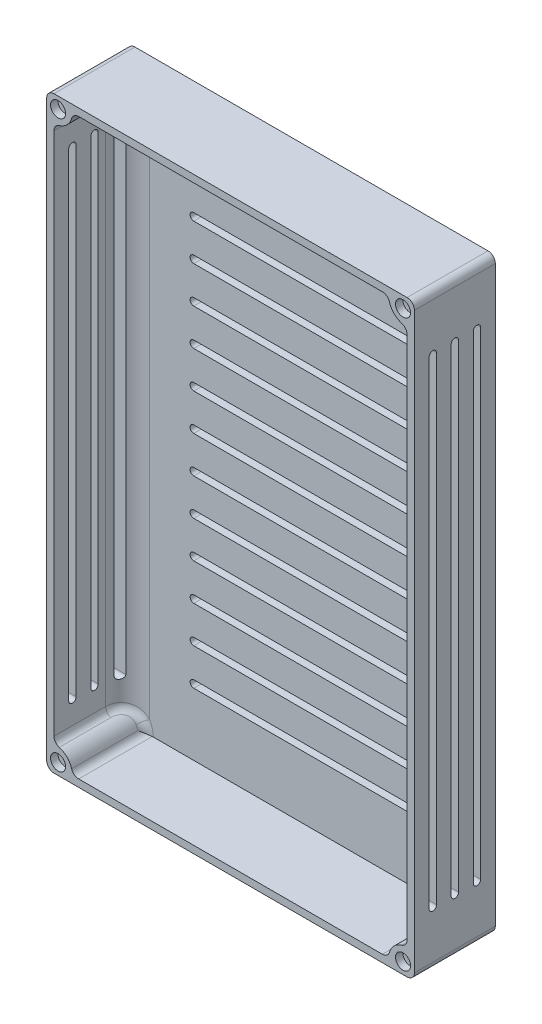
SolidWorks part; units mm, degrees
ref_plane "Front Plane" through (0, 0, 0) normal (1, 0, 0) x (0, 1, 0)
ref_plane "Top Plane" through (0, 0, 0) normal (0, 0, 1) x (0, 1, 0)
ref_plane "Right Plane" through (0, 0, 0) normal (0, 1, 0) x (-1, 0, 0)
ref_axis "x axis" through (-88.99, 0, 0) along (1, 0, 0)
ref_axis "y xxis" through (0, 88.99, 0) along (0, -1, 0)
ref_axis "z axis" through (0, 0, 55) along (0, 0, -1)
sketch "Sketch1" plane through (0, 0, 0) normal (0, 0, 1) x (0, 1, 0)
  line L1 (-80, -50) -> (80, -50)
  line L2 (-80, -50) -> (-80, 50)
  line L3 (-80, 50) -> (80, 50)
  line L4 (80, -50) -> (80, 50)
  line L5 (-80, -50) -> (80, 50) construction
  line L6 (-80, 50) -> (80, -50) construction
  point P0 (0, 0)
  dimension "D1" = 100
  dimension "D2" = 160
extrude "Boss-Extrude1" add sketch "Sketch1" along normal blind 2
sketch "Sketch2" plane through (0, 0, 2) normal (0, 0, 1) x (1, 0, 0)
  line L0 (0, -55) -> (0, 55) construction
  line L1 (55, 0) -> (-55, 0) construction
  line L4 (-48, 73) -> (-48, -73)
  line L5 (-43, -78) -> (43, -78)
  line L6 (48, -73) -> (48, 73)
  line L7 (43, 78) -> (-43, 78)
  line L8 (50, 80) -> (-50, 80)
  line L9 (-50, 80) -> (-50, -80)
  line L10 (-50, -80) -> (50, -80)
  line L11 (50, -80) -> (50, 80)
  line L12 (50, 80) -> (-50, 80)
  line L13 (-50, 80) -> (-50, -80)
  line L14 (-50, -80) -> (50, -80)
  line L15 (50, -80) -> (50, 80)
  line L16 (-48, 78) -> (-48, -78) construction
  line L17 (-48, -78) -> (48, -78) construction
  line L18 (48, -78) -> (48, 78) construction
  line L19 (48, 78) -> (-48, 78) construction
  arc A4 (-48, 73) -> (-43, 78) centre (-48, 78) ccw
  arc A5 (48, 73) -> (43, 78) centre (48, 78) cw
  arc A6 (48, -73) -> (43, -78) centre (48, -78) ccw
  arc A7 (-48, -73) -> (-43, -78) centre (-48, -78) cw
  point P6 (-43.9242, -73)
  point P11 (-48, -68.8643)
  point P12 (43.8879, -73)
  point P13 (0, 0)
  point P14 (48, -68.8626)
  point P15 (48, 68.915)
  point P16 (0, 0)
  point P19 (0, 0)
  point P33 (43.918, 73)
  dimension "D3" = 5
  dimension "D2" = 2
  dimension "D1" = 0
extrude "Boss-Extrude2" add sketch "Sketch2" along normal blind 20
sketch "Sketch3" plane through (0, 0, 22) normal (0, 0, 1) x (1, 0, 0)
  line L0 (-46.9, 76.9) -> (-50, 76.9) construction
  line L1 (-50, 80) -> (-50, -80) construction
  line L2 (-46.9, 76.9) -> (-46.9, 80) construction
  line L3 (50, 80) -> (-50, 80) construction
  line L4 (0, 0) -> (0, 37.5052) construction
  line L5 (0, 0) -> (18.9658, 0) construction
  circle A0 centre (-46.9, 76.9) radius 2.05
  circle A1 centre (46.9, 76.9) radius 2.05
  circle A2 centre (46.9, -76.9) radius 2.05
  circle A3 centre (-46.9, -76.9) radius 2.05
  dimension "D1" = 4.1
  dimension "D2" = 3.1
extrude "Cut-Extrude1" cut sketch "Sketch3" against normal blind 2
fillet "Fillet1" radius 6 2 edges at (-48, 0, 2) (48, 0, 2)
fillet "Fillet2" radius 2 12 edges at (45.6534, -73.5849, 3.2405) (45.0847, 73.9379, 2.8537) (43, -78, 12.042) (48, -73, 15) (48, 73, 15) (43, 78, 12.042) (-45.6534, 73.5849, 3.2405) (-45.0847, -73.9379, 2.8537) (-43, 78, 12.042) (-48, 73, 15) (-48, -73, 15) (-43, -78, 12.042)
sketch "Sketch4" plane through (0, 0, 0) normal (0, 0, -1) x (1, 0, 0)
  circle A0 centre (-46.9, 76.9) radius 2.05
  circle A1 centre (46.9, 76.9) radius 2.05
  circle A2 centre (46.9, -76.9) radius 2.05
  circle A3 centre (-46.9, -76.9) radius 2.05
  circle A4 centre (-46.9, -76.9) radius 2.05 construction
  circle A5 centre (46.9, -76.9) radius 2.05 construction
  circle A6 centre (-46.9, 76.9) radius 2.05 construction
  circle A7 centre (46.9, 76.9) radius 2.05 construction
extrude "Cut-Extrude2" cut sketch "Sketch4" against normal blind 2
sketch "Sketch7" plane through (0, 0, 2) normal (0, 0, 1) x (1, 0, 0)
  line L0 (-30, 60) -> (30, 60) construction
  line L1 (-30, 61) -> (30, 61)
  line L2 (-30, 59) -> (30, 59)
  line L3 (0, 0) -> (0, 60) construction
  line L4 (-30, 50) -> (30, 50) construction
  line L5 (-30, 51) -> (30, 51)
  line L6 (-30, 49) -> (30, 49)
  line L7 (-30, 40) -> (30, 40) construction
  line L8 (-30, 41) -> (30, 41)
  line L9 (-30, 39) -> (30, 39)
  line L10 (-30, 30) -> (30, 30) construction
  line L11 (-30, 31) -> (30, 31)
  line L12 (-30, 29) -> (30, 29)
  line L13 (-30, 20) -> (30, 20) construction
  line L14 (-30, 21) -> (30, 21)
  line L15 (-30, 19) -> (30, 19)
  line L16 (-30, 10) -> (30, 10) construction
  line L17 (-30, 11) -> (30, 11)
  line L18 (-30, 9) -> (30, 9)
  line L19 (-30, 0) -> (30, 0) construction
  line L20 (-30, 1) -> (30, 1)
  line L21 (-30, -1) -> (30, -1)
  line L22 (-30, -10) -> (30, -10) construction
  line L23 (-30, -9) -> (30, -9)
  line L24 (-30, -11) -> (30, -11)
  line L25 (-30, -20) -> (30, -20) construction
  line L26 (-30, -19) -> (30, -19)
  line L27 (-30, -21) -> (30, -21)
  line L28 (-30, -30) -> (30, -30) construction
  line L29 (-30, -29) -> (30, -29)
  line L30 (-30, -31) -> (30, -31)
  line L31 (-30, -40) -> (30, -40) construction
  line L32 (-30, -39) -> (30, -39)
  line L33 (-30, -41) -> (30, -41)
  line L34 (-30, -50) -> (30, -50) construction
  line L35 (-30, -49) -> (30, -49)
  line L36 (-30, -51) -> (30, -51)
  line L37 (-30, -60) -> (30, -60) construction
  line L38 (-30, -59) -> (30, -59)
  line L39 (-30, -61) -> (30, -61)
  arc A0 (-30, 61) -> (-30, 59) centre (-30, 60) ccw
  arc A1 (30, 59) -> (30, 61) centre (30, 60) ccw
  arc A2 (-30, 51) -> (-30, 49) centre (-30, 50) ccw
  arc A3 (30, 49) -> (30, 51) centre (30, 50) ccw
  arc A4 (-30, 41) -> (-30, 39) centre (-30, 40) ccw
  arc A5 (30, 39) -> (30, 41) centre (30, 40) ccw
  arc A6 (-30, 31) -> (-30, 29) centre (-30, 30) ccw
  arc A7 (30, 29) -> (30, 31) centre (30, 30) ccw
  arc A8 (-30, 21) -> (-30, 19) centre (-30, 20) ccw
  arc A9 (30, 19) -> (30, 21) centre (30, 20) ccw
  arc A10 (-30, 11) -> (-30, 9) centre (-30, 10) ccw
  arc A11 (30, 9) -> (30, 11) centre (30, 10) ccw
  arc A12 (-30, 1) -> (-30, -1) centre (-30, 0) ccw
  arc A13 (30, -1) -> (30, 1) centre (30, 0) ccw
  arc A14 (-30, -9) -> (-30, -11) centre (-30, -10) ccw
  arc A15 (30, -11) -> (30, -9) centre (30, -10) ccw
  arc A16 (-30, -19) -> (-30, -21) centre (-30, -20) ccw
  arc A17 (30, -21) -> (30, -19) centre (30, -20) ccw
  arc A18 (-30, -29) -> (-30, -31) centre (-30, -30) ccw
  arc A19 (30, -31) -> (30, -29) centre (30, -30) ccw
  arc A20 (-30, -39) -> (-30, -41) centre (-30, -40) ccw
  arc A21 (30, -41) -> (30, -39) centre (30, -40) ccw
  arc A22 (-30, -49) -> (-30, -51) centre (-30, -50) ccw
  arc A23 (30, -51) -> (30, -49) centre (30, -50) ccw
  arc A24 (-30, -59) -> (-30, -61) centre (-30, -60) ccw
  arc A25 (30, -61) -> (30, -59) centre (30, -60) ccw
  point P2 (0, 60)
  point P13 (0, 50)
  point P20 (0, 40)
  point P27 (0, 30)
  point P34 (0, 20)
  point P41 (0, 10)
  point P48 (0, 0)
  point P55 (0, -10)
  point P62 (0, -20)
  point P69 (0, -30)
  point P76 (0, -40)
  point P83 (0, -50)
  point P90 (0, -60)
  dimension "D1" = 1
  dimension "D2" = 60
  dimension "D4" = 60
  dimension "D3" = 13
extrude "Cut-Extrude3" cut sketch "Sketch7" against normal up to surface (2 mm away) up to face at (-48.95, 76.9, 0)
fillet "Fillet4" radius 2 4 edges at (50, -80, 11) (-50, -80, 11) (-50, 80, 11) (50, 80, 11)
sketch "Sketch8" plane through (50, 0, 0) normal (1, 0, 0) x (0, 1, 0)
  line L0 (-65, 17) -> (65, 17) construction
  line L1 (-65, 18) -> (65, 18)
  line L2 (-65, 16) -> (65, 16)
  line L3 (0, 17) -> (0, 0) construction
  line L6 (-65, 11) -> (65, 11) construction
  line L7 (-65, 12) -> (65, 12)
  line L8 (-65, 10) -> (65, 10)
  line L9 (-65, 5) -> (65, 5) construction
  line L10 (-65, 6) -> (65, 6)
  line L11 (-65, 4) -> (65, 4)
  arc A0 (-65, 18) -> (-65, 16) centre (-65, 17) ccw
  arc A1 (65, 16) -> (65, 18) centre (65, 17) ccw
  arc A4 (-65, 12) -> (-65, 10) centre (-65, 11) ccw
  arc A5 (65, 10) -> (65, 12) centre (65, 11) ccw
  arc A6 (-65, 6) -> (-65, 4) centre (-65, 5) ccw
  arc A7 (65, 4) -> (65, 6) centre (65, 5) ccw
  point P2 (0, 17)
  point P13 (0, 11)
  point P20 (0, 5)
  dimension "D2" = 1
  dimension "D1" = 130
  dimension "D4" = 17
  dimension "D3" = 3
extrude "Cut-Extrude4" cut sketch "Sketch8" against normal up to surface (100 mm away) up to face at (-50, 0, 11)
